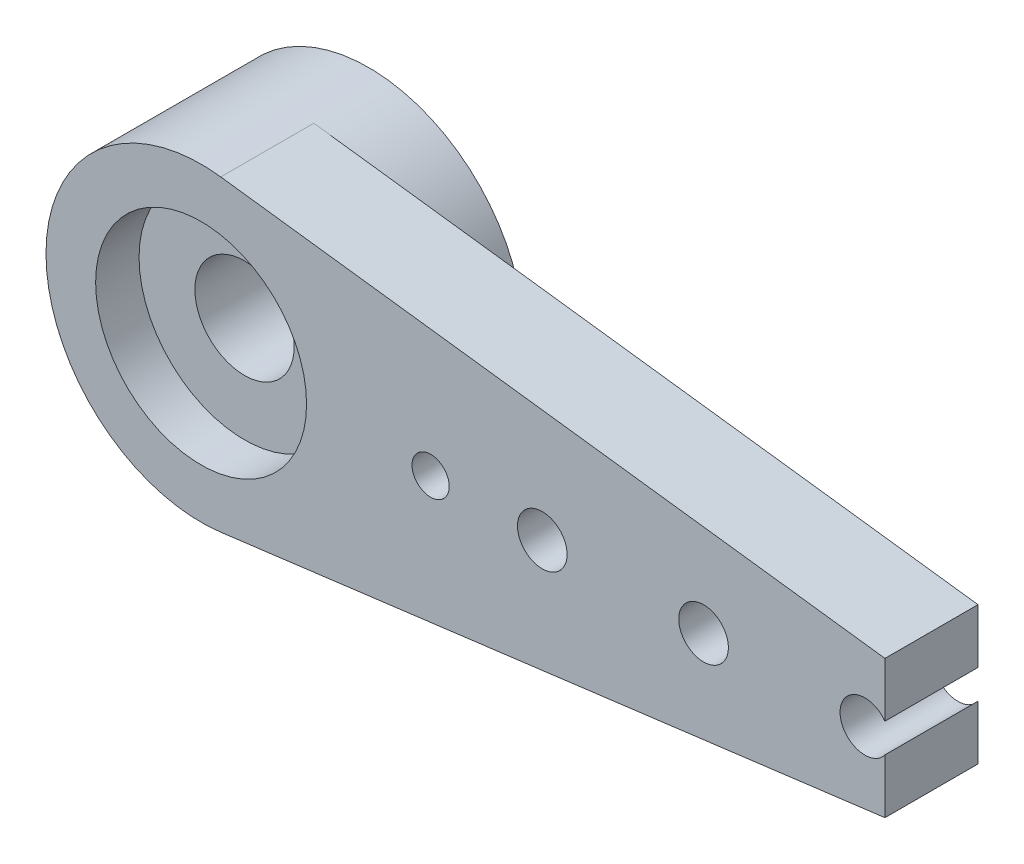
SolidWorks part; units mm, degrees
note: '?' marks a value the reader was unsure of. The reader was unsure of these and kept them because the rebuilt part matched: shared geometry of "Sketch1<3>".
ref_plane "Front Plane" through (0, 0, 0) normal (0, 0, 1) x (1, 0, 0)
ref_plane "Top Plane" through (0, 0, 0) normal (0, 1, 0) x (1, 0, 0)
ref_plane "Right Plane" through (0, 0, 0) normal (1, 0, 0) x (0, 0, -1)
sketch "Sketch1" plane through (0, 0, 0) normal (0, 0, 1) x (1, 0, 0)
  line L0 (0.4023, 3.1494) -> (17.6594, 0.9448)
  line L1 (0, 0) -> (17.5387, 0) construction
  line L2 (0.4023, -3.1494) -> (17.6594, -0.9448)
  line L3 (-3.175, 0) -> (-3.175, 3.8612) construction
  line L4 (18.4912, 0) -> (18.4912, 2.8196) construction
  circle A0 centre (0, 0) radius 3.175
  circle A1 centre (0, 0) radius 1.016
  circle A2 centre (17.5387, 0) radius 0.9525
  circle A3 centre (4.699, 0) radius 0.381
  circle A4 centre (6.985, 0) radius 0.508
  circle A5 centre (10.287, 0) radius 0.508
  circle A6 centre (16.891, 0) radius 0.508
  circle A7 centre (13.589, 0) radius 0.508
  point P24 (5.6135, 0)
  dimension "D1" = 6.35
  dimension "1.5/2" = 1.905
  dimension "D3" = 21.6662
  dimension "D4" = 2.032
  dimension "D5" = 0.762
  dimension "D6" = 1.016
  dimension "D7" = 1.016
  dimension "D8" = 1.016
  dimension "D9" = 1.016
  dimension "D10" = 7.874
  dimension "D11" = 10.16
  dimension "D12" = 3.302
  dimension "D13" = 3.302
  dimension "D14" = 3.302
extrude "Boss-Extrude1" add sketch "Sketch1" along normal blind 1.905 contours A0 A1 | A2 L0 A0 L2 A7 A6 A5 A4 A3 | A2
extrude "Boss-Extrude2" add sketch "Sketch1<3>" against normal blind 1.524 contours A0 A1
sketch "Sketch1<3>" plane through (0, 0, 0) normal (0, 0, 1) x (1, 0, 0) same geometry as "Sketch1"
sketch "Sketch2" plane through (0, 0, 1.905) normal (0, 0, 1) x (1, 0, 0)
  line L2 (0.4023, -3.1494) -> (17.6594, -0.9448)
  line L3 (17.6594, 0.9448) -> (0.4023, 3.1494)
  line L4 (0.4023, -3.1494) -> (17.6594, -0.9448)
  line L5 (17.6594, 0.9448) -> (0.4023, 3.1494)
  circle A0 centre (0, 0) radius 1.016 construction
  circle A1 centre (0, 0) radius 1.016
  arc A2 (0.4023, 3.1494) -> (0.4023, -3.1494) centre (0, 0) ccw
  arc A3 (17.6594, -0.9448) -> (17.6594, 0.9448) centre (17.5387, 0) ccw
  arc A4 (0.4023, 3.1494) -> (0.4023, -3.1494) centre (0, 0) ccw
  arc A5 (17.6594, -0.9448) -> (17.6594, 0.9448) centre (17.5387, 0) ccw
  circle A6 centre (0, 0) radius 2.159
  circle M6 centre (0, 0) radius 1.016
  dimension "D2" = 4.318
  dimension "D1" = 0
extrude "Cut-Extrude1" cut sketch "Sketch2" against normal blind 0.889 contours A6 M6
sketch "Sketch4" plane through (0, 0, -1.524) normal (0, 0, -1) x (-1, 0, 0)
  circle A0 centre (0, 0) radius 2.0955
  circle A1 centre (0, 0) radius 1.016
  circle A2 centre (0, 0) radius 1.016
  dimension "D2" = 4.191
  dimension "D1" = 0
extrude "Cut-Extrude2" cut sketch "Sketch4" against normal blind 0.889
ref_axis "Axis1" through (0, 0, 0) along (1, 0, 0)?
sketch "Sketch5" plane through (0, 0, 0) normal (0, 0, -1) x (-1, 0, 0)
  line L0 (0, 0) -> (-17.5387, 0) construction
  line L1 (-14, -4.163) -> (0, -4.163)
  line L2 (-17.6594, -0.9448) -> (-0.4023, -3.1494)
  line L3 (-0.4023, 3.1494) -> (-17.6594, 0.9448)
  line L4 (-17.6594, -0.9448) -> (-0.4023, -3.1494)
  line L5 (-0.4023, 3.1494) -> (-17.6594, 0.9448)
  line L6 (-14, -4.163) -> (-14, 4.163)
  line L7 (-14, 4.163) -> (0, 4.163)
  line L8 (0, -4.163) -> (0, 4.163)
  line L9 (-14, -4.163) -> (0, 4.163) construction
  line L10 (-14, 4.163) -> (0, -4.163) construction
  line L12 (-14, 4.163) -> (-21.2304, 4.163)
  line L13 (-14, 4.163) -> (-14, -4.163)
  line L14 (-14, -4.163) -> (-21.2304, -4.163)
  line L15 (-21.2304, 4.163) -> (-21.2304, -4.163)
  circle A1 centre (0, 0) radius 3.175
  arc A2 (-0.4023, 3.1494) -> (-0.4023, -3.1494) centre (0, 0) ccw
  arc A3 (-17.6594, 0.9448) -> (-17.6594, -0.9448) centre (-17.5387, 0) ccw
  arc A4 (-0.4023, 3.1494) -> (-0.4023, -3.1494) centre (0, 0) ccw
  arc A5 (-17.6594, 0.9448) -> (-17.6594, -0.9448) centre (-17.5387, 0) ccw
  circle A6 centre (0, 0) radius 3.175
  point P2 (-7, 0)
  circle M14 centre (-16.891, 0) radius 0.508
  line M15 (-17.6594, -0.9448) -> (-0.4023, -3.1494)
  arc M18 (-17.6594, 0.9448) -> (-17.6594, -0.9448) centre (-17.5387, 0) ccw
  circle M19 centre (-13.589, 0) radius 0.508
  dimension "D3" = 14
  dimension "D1" = 0
  dimension "D2" = 0
extrude "Cut-Extrude3" cut sketch "Sketch5" against normal through all both and the other way through all contours L6 L5 M15 M19 M18 M14 | M14
